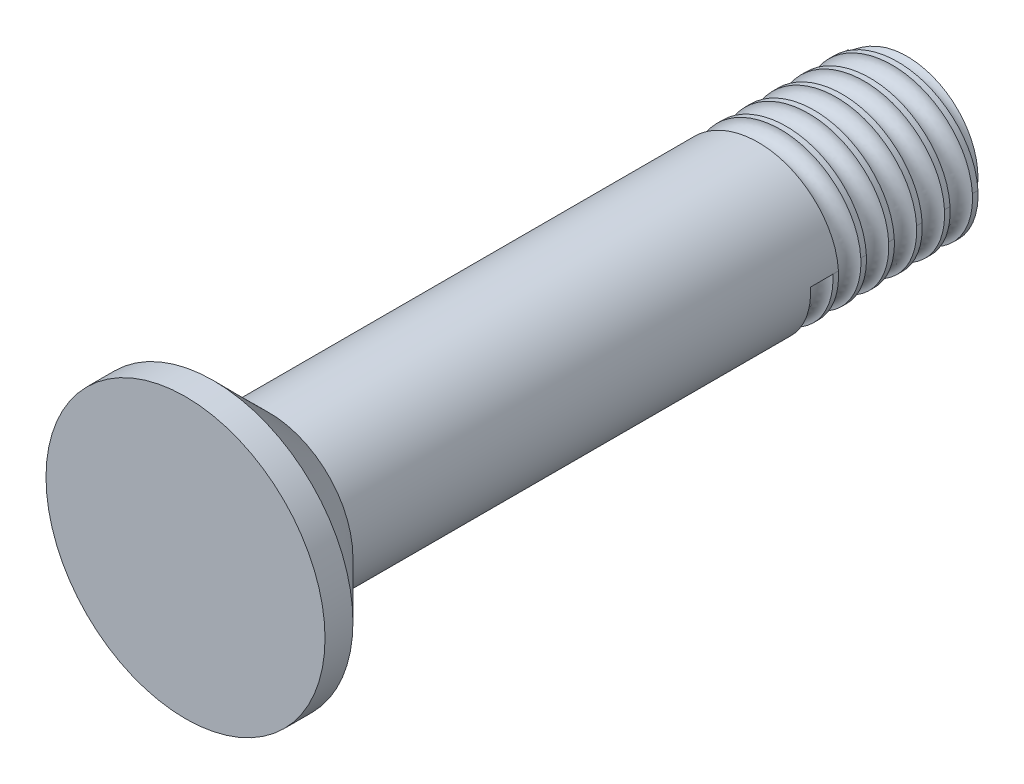
SolidWorks part; units mm, degrees
ref_plane "Front Plane" through (0, 0, 0) normal (0, 0, 1) x (1, 0, 0)
ref_plane "Top Plane" through (0, 0, 0) normal (0, 1, 0) x (1, 0, 0)
ref_plane "Right Plane" through (0, 0, 0) normal (1, 0, 0) x (0, 0, -1)
sketch "Sketch1" plane through (0, 0, 0) normal (0, 0, 1) x (1, 0, 0)
  circle A0 centre (0, 0) radius 1.4
extrude "Extrude1" add sketch "Sketch1" along normal blind 13
sketch "Sketch3" plane through (0, 0, 13) normal (0, 0, 1) x (1, 0, 0)
  circle A0 centre (0, 0) radius 2.5
extrude "Extrude2" add sketch "Sketch3" against normal blind 1.5
sketch "Sketch4" plane through (0, 0, 0) normal (0, 0, -1) x (-1, 0, 0)
  circle A0 centre (0, 0) radius 1.4
curve "Helix/Spiral1" pitch 0.5 height 3 turns 6
sketch "Sketch5" plane through (0, 0, 0) normal (0, 1, 0) x (1, 0, 0)
  line L0 (1.4, 0) -> (-1.4, 0) construction
  circle A0 centre (1.4, 0) radius 0.2
  spline S0 degree 3 poles (1.4, 0) (1.4, -0.0104) (1.3271, -0.0313) (1.0157, -0.0625) (0.5497, -0.0938) (0, -0.125) (-0.5497, -0.1563) (-1.0157, -0.1875) (-1.3271, -0.2188) (-1.4364, -0.25) (-1.3271, -0.2813) (-1.0157, -0.3125) (-0.5497, -0.3438) (0, -0.375) (0.5497, -0.4063) (1.0157, -0.4375) (1.3271, -0.4688) (1.4364, -0.5) (1.3271, -0.5313) (1.0157, -0.5625) (0.5497, -0.5938) (0, -0.625) (-0.5497, -0.6563) (-1.0157, -0.6875) (-1.3271, -0.7188) (-1.4364, -0.75) (-1.3271, -0.7813) (-1.0157, -0.8125) (-0.5497, -0.8438) (0, -0.875) (0.5497, -0.9063) (1.0157, -0.9375) (1.3271, -0.9688) (1.4364, -1) (1.3271, -1.0313) (1.0157, -1.0625) (0.5497, -1.0938) (0, -1.125) (-0.5497, -1.1563) (-1.0157, -1.1875) (-1.3271, -1.2188) (-1.4364, -1.25) (-1.3271, -1.2813) (-1.0157, -1.3125) (-0.5497, -1.3438) (0, -1.375) (0.5497, -1.4063) (1.0157, -1.4375) (1.3271, -1.4688) (1.4364, -1.5) (1.3271, -1.5313) (1.0157, -1.5625) (0.5497, -1.5938) (0, -1.625) (-0.5497, -1.6563) (-1.0157, -1.6875) (-1.3271, -1.7188) (-1.4364, -1.75) (-1.3271, -1.7813) (-1.0157, -1.8125) (-0.5497, -1.8438) (0, -1.875) (0.5497, -1.9063) (1.0157, -1.9375) (1.3271, -1.9688) (1.4364, -2) (1.3271, -2.0313) (1.0157, -2.0625) (0.5497, -2.0938) (0, -2.125) (-0.5497, -2.1563) (-1.0157, -2.1875) (-1.3271, -2.2188) (-1.4364, -2.25) (-1.3271, -2.2813) (-1.0157, -2.3125) (-0.5497, -2.3438) (0, -2.375) (0.5497, -2.4063) (1.0157, -2.4375) (1.3271, -2.4687) (1.4364, -2.5) (1.3271, -2.5312) (1.0157, -2.5625) (0.5497, -2.5937) (0, -2.625) (-0.5497, -2.6562) (-1.0157, -2.6875) (-1.3271, -2.7187) (-1.4364, -2.75) (-1.3271, -2.7812) (-1.0157, -2.8125) (-0.5497, -2.8437) (0, -2.875) (0.5497, -2.9062) (1.0157, -2.9375) (1.3271, -2.9687) (1.4, -2.9896) (1.4, -3) knots 0 0 0 0 0.010417 0.020833 0.03125 0.041667 0.052083 0.0625 0.072917 0.083333 0.09375 0.104167 0.114583 0.125 0.135417 0.145833 0.15625 0.166667 0.177083 0.1875 0.197917 0.208333 0.21875 0.229167 0.239583 0.25 0.260417 0.270833 0.28125 0.291667 0.302083 0.3125 0.322917 0.333333 0.34375 0.354167 0.364583 0.375 0.385417 0.395833 0.40625 0.416667 0.427083 0.4375 0.447917 0.458333 0.46875 0.479167 0.489583 0.5 0.510417 0.520833 0.53125 0.541667 0.552083 0.5625 0.572917 0.583333 0.59375 0.604167 0.614583 0.625 0.635417 0.645833 0.65625 0.666667 0.677083 0.6875 0.697917 0.708333 0.71875 0.729167 0.739583 0.75 0.760417 0.770833 0.78125 0.791667 0.802083 0.8125 0.822917 0.833333 0.84375 0.854167 0.864583 0.875 0.885417 0.895833 0.90625 0.916667 0.927083 0.9375 0.947917 0.958333 0.96875 0.979167 0.989583 1 1 1 1 construction
sweep "Cut-Sweep1" cut profiles "Sketch5" path "Helix/Spiral1"
chamfer "Chamfer1" distance 1 angle 45 1 edges at (2.5, 0, 11.5)
